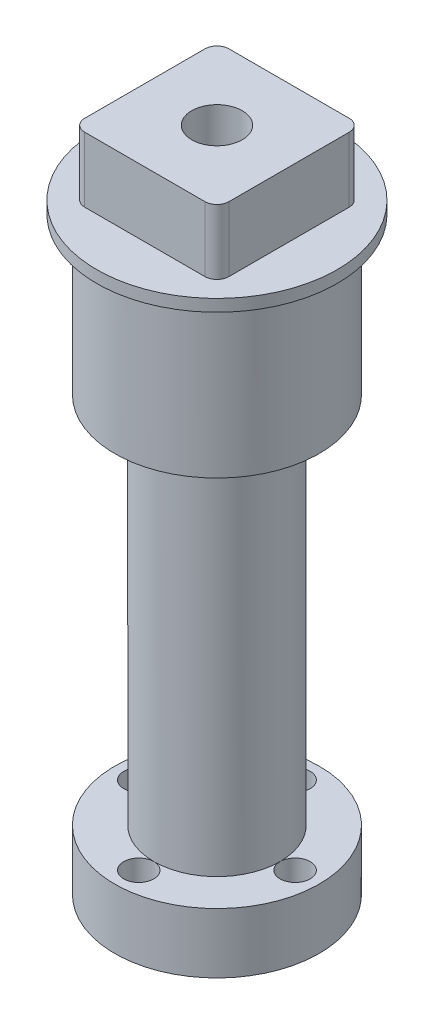
SolidWorks part; units mm, degrees
material "6061-T6 (SS)"
ref_plane "前视基准面" through (0, 0, 0) normal (0, 0, 1) x (1, 0, 0)
ref_plane "上视基准面" through (0, 0, 0) normal (0, 1, 0) x (1, 0, 0)
ref_plane "右视基准面" through (0, 0, 0) normal (1, 0, 0) x (0, 0, -1)
sketch "草图1" plane through (0, 0, 0) normal (0, 0, 1) x (1, 0, 0)
  line L0 (0, 0) -> (0, 22.2724) construction
  line L1 (-8.5, 36) -> (-5.25, 36)
  line L2 (-4.25, 0) -> (-8.5, 0)
  line L3 (-4.25, 0) -> (-4.25, 50)
  line L4 (-4.25, 50) -> (-8.5, 50)
  line L5 (-8.5, 0) -> (-8.5, 5)
  line L6 (-5.25, 36) -> (-5.25, 5)
  line L7 (-5.25, 5) -> (-8.5, 5)
  line L8 (-8.5, 36) -> (-8.5, 50)
  dimension "D1" = 8.5
  dimension "D2" = 17
  dimension "D3" = 50
  dimension "D4" = 36
  dimension "D5" = 5
  dimension "D6" = 1
revolve "旋转1" add sketch "草图1" angle 360 about L0
sketch "草图2" plane through (0, 50, 0) normal (0, 1, 0) x (1, 0, 0)
  circle A0 centre (0, 0) radius 6.5 construction
  circle A1 centre (0, 6.5) radius 1.25
  circle A2 centre (0, -6.5) radius 1.25
  circle A3 centre (-6.5, 0) radius 1.25
  circle A4 centre (6.5, 0) radius 1.25
  dimension "D1" = 13
  dimension "D2" = 2.5
extrude "切除-拉伸2" cut sketch "草图2" along normal blind 6 from surface starting at face at (0, 0, -4.25)
cosmetic thread "装饰螺纹线1" parameters "D2"=3
cosmetic thread "装饰螺纹线2" parameters "D2"=3
sketch "草图4" plane through (0, 50, 0) normal (0, 1, 0) x (1, 0, 0)
  line L1 (-6, 6) -> (6, 6)
  line L2 (-6, 6) -> (-6, -6)
  line L3 (-6, -6) -> (6, -6)
  line L4 (6, 6) -> (6, -6)
  line L5 (-6, 6) -> (6, -6) construction
  line L6 (-6, -6) -> (6, 6) construction
  point P0 (0, 0)
  dimension "D1" = 12
extrude "凸台-拉伸1" add sketch "草图4" along normal blind 5.4
fillet "圆角1" radius 1 4 edges at (6, 52.7, 6) (-6, 52.7, 6) (6, 52.7, -6) (-6, 52.7, -6)
sketch "草图5" plane through (0, 0, 0) normal (0, 0, 1) x (1, 0, 0)
  line L0 (0, 0) -> (0, 55.4) construction
  line L1 (-8.5, 50) -> (-10, 50)
  line L2 (-8.5, 50) -> (-8.5, 49)
  line L3 (-8.5, 49) -> (-10, 49)
  line L4 (-10, 50) -> (-10, 49)
  line L5 (5, 55.4) -> (-5, 55.4) construction
  dimension "D1" = 1.5
  dimension "D2" = 1
revolve "旋转2" add sketch "草图5" angle 360 about L0
sketch "草图6" plane through (0, 50, 0) normal (0, -1, 0) x (1, 0, 0)
  circle A1 centre (0, 0) radius 4.25
  circle A2 centre (0, 0) radius 4.25
  dimension "D1" = 0
extrude "凸台-拉伸2" add sketch "草图6" along normal blind 6
hole_wizard "M5 螺纹孔2" positions "草图10" profile "草图9" tap size "M5" standard "ISO" end condition through all
sketch "草图10" plane through (0, 55.4, 0) normal (0, 1, 0) x (1, 0, 0)
  point P0 (0, 0)
sketch "草图9" plane through (0, 55.4, 0) normal (1, 0, 0) x (0, 0, 1)
  line L0 (0, 0) -> (0, 55.4)
  line L1 (0, 55.4) -> (2.1, 55.4)
  line L2 (2.1, 55.4) -> (2.1, 0)
  line L5 (2.1, 0) -> (0, 0)
  line L11 (0, -6.35) -> (0, 107.95) construction
  dimension "通孔螺纹孔钻头直径" = 4.2
  dimension "通孔螺纹孔钻头深度" = 55.4
cosmetic thread "孔螺蚊线2" parameters "D2"=5
